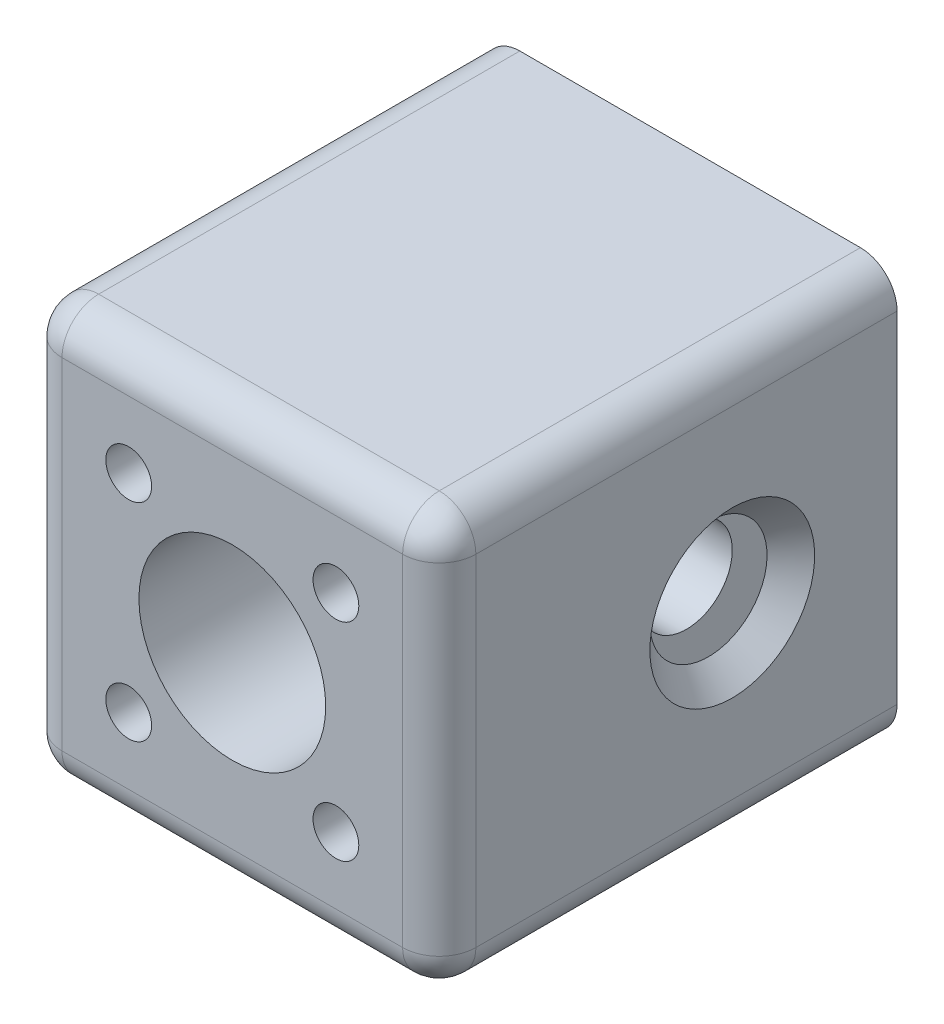
SolidWorks part; units mm, degrees
ref_plane "Alzado" through (0, 0, 0) normal (0, 0, 1) x (1, 0, 0)
ref_plane "Planta" through (0, 0, 0) normal (0, 1, 0) x (1, 0, 0)
ref_plane "Vista lateral" through (0, 0, 0) normal (1, 0, 0) x (0, 0, -1)
sketch "Croquis1" plane through (0, 0, 0) normal (0, 0, 1) x (1, 0, 0)
  line L1 (-11.3, 11.3) -> (11.3, 11.3)
  line L2 (-11.3, 11.3) -> (-11.3, -11.3)
  line L3 (-11.3, -11.3) -> (11.3, -11.3)
  line L4 (11.3, 11.3) -> (11.3, -11.3)
  line L5 (-11.3, 11.3) -> (11.3, -11.3) construction
  line L6 (-11.3, -11.3) -> (11.3, 11.3) construction
  line L11 (-10, 10) -> (10, -10) construction
  line L12 (-10, -10) -> (10, 10) construction
  point P0 (0, 0)
  point P5 (0, 0)
  dimension "D1" = 22.6
  dimension "D2" = 22.6
extrude "Saliente-Extruir1" add sketch "Croquis1" along normal blind 25
sketch "Croquis2" plane through (0, 0, 25) normal (0, 0, 1) x (1, 0, 0)
  circle A0 centre (0, 0) radius 5.1
  dimension "D1" = 10.2
extrude "Cortar-Extruir1" cut sketch "Croquis2" against normal through all
sketch "Croquis3" plane through (0, 0, 25) normal (0, 0, 1) x (1, 0, 0)
  line L0 (0, 0) -> (11.3, 11.3) construction
  circle A0 centre (5.6569, 5.6569) radius 1.25
  circle A1 centre (5.6569, -5.6569) radius 1.25
  circle A2 centre (-5.6569, -5.6569) radius 1.25
  circle A3 centre (-5.6569, 5.6569) radius 1.25
  point P15 (0, 0)
  dimension "D1" = 2.5
  dimension "D2" = 8
  dimension "D3" = 4
extrude "Cortar-Extruir2" cut sketch "Croquis3" against normal through all
sketch "Croquis4" plane through (0, 0, 0) normal (0, 0, -1) x (-1, 0, 0)
  line L0 (-8.8, 8.8) -> (8.8, 8.8)
  line L1 (-10, 10) -> (10, 10)
  line L2 (-10, 10) -> (-10, -10)
  line L3 (-10, -10) -> (10, -10)
  line L4 (10, 10) -> (10, -10)
  line L5 (-10, 10) -> (10, -10) construction
  line L6 (-10, -10) -> (10, 10) construction
  line L7 (8.8, 8.8) -> (8.8, -8.8)
  line L8 (-8.8, -8.8) -> (8.8, -8.8)
  line L9 (-8.8, 8.8) -> (-8.8, -8.8)
  point P0 (0, 0)
  dimension "D1" = 20
  dimension "D2" = 20
  dimension "D3" = 1.2
extrude "Cortar-Extruir3" cut sketch "Croquis4" against normal blind 15
sketch "Croquis5" plane through (11.3, 0, 0) normal (1, 0, 0) x (0, 0, -1)
  line L0 (0, 0) -> (-25, 0) construction
  line L1 (-25, -11.3) -> (-25, 11.3) construction
  circle A0 centre (-9, 0) radius 2.5
  dimension "D1" = 5
  dimension "D2" = 9
extrude "Cortar-Extruir4" cut sketch "Croquis5" against normal through all
chamfer "Chaflán1" distance 2 angle 45 2 edges at (-11.3, 2.5, 9) (11.3, 2.5, 9)
fillet "Redondeo1" radius 2 4 edges at (-11.3, -11.3, 12.5) (11.3, -11.3, 12.5) (-11.3, 11.3, 12.5) (11.3, 11.3, 12.5)
fillet "Redondeo2" radius 2 8 edges at (10.7142, 10.7142, 25) (11.3, 0, 25) (10.7142, -10.7142, 25) (0, -11.3, 25) (-10.7142, -10.7142, 25) (-11.3, 0, 25) (-10.7142, 10.7142, 25) (0, 11.3, 25)
sketch "Croquis6" plane through (0, -11.3, 0) normal (0, -1, 0) x (1, 0, 0)
  line L0 (-9.3, 11.5) -> (9.3, 11.5) construction
  line L1 (-9.3, 23) -> (-9.3, 0) construction
  line L2 (9.3, 0) -> (9.3, 23) construction
  text T0 "FRONT" font "Arial" height 3.5
